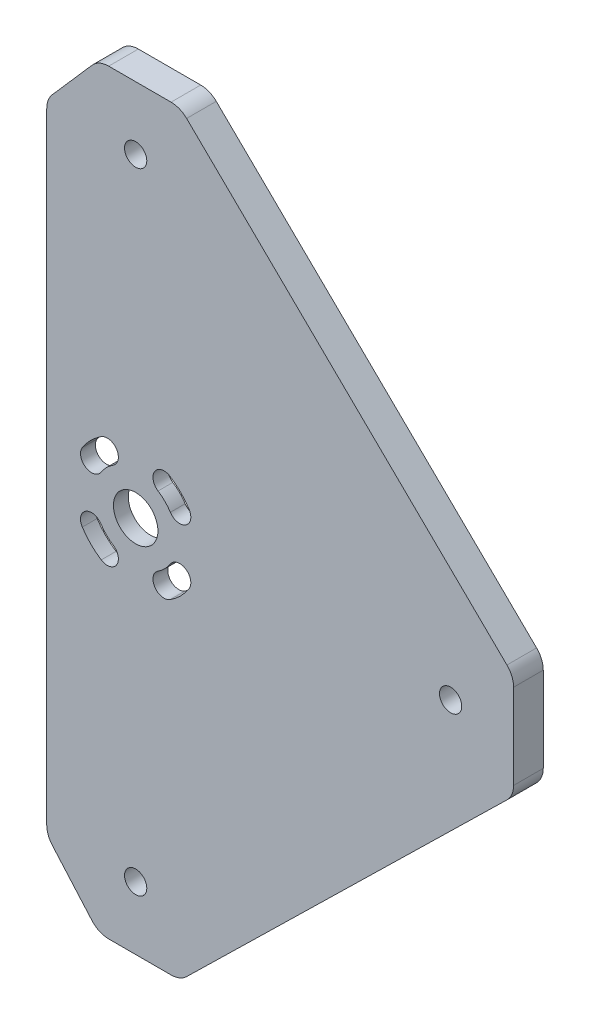
SolidWorks part; units mm, degrees
ref_plane "前视基准面" through (0, 0, 0) normal (0, 0, 1) x (1, 0, 0)
ref_plane "上视基准面" through (0, 0, 0) normal (0, 1, 0) x (1, 0, 0)
ref_plane "右视基准面" through (0, 0, 0) normal (1, 0, 0) x (0, 0, -1)
sketch "草图1" plane through (0, 0, 0) normal (0, 0, 1) x (1, 0, 0)
  line L0 (1791.9751, 1614.3835) -> (1791.9751, 1566.6287) construction
  line L1 (1789.8715, 1561.5082) -> (1789.8715, 1513.7534) construction
  line L2 (1807.2571, 1618.4717) -> (1860.0947, 1562.7534) construction
  line L3 (1860.0947, 1562.7534) -> (1809.6082, 1499.3687) construction
  line L4 (1789.5396, 1516.1637) -> (1794.9009, 1510.0365)
  line L5 (1797.1587, 1509.012) -> (1805.5744, 1509.012)
  line L6 (1807.6718, 1509.867) -> (1850.8947, 1552.1294)
  line L7 (1851.7974, 1554.2744) -> (1851.7974, 1565.7496)
  line L8 (1850.8947, 1567.8946) -> (1807.6718, 1610.157)
  line L9 (1805.5744, 1611.012) -> (1797.1587, 1611.012)
  line L10 (1794.9009, 1609.9875) -> (1789.5396, 1603.8603)
  line L11 (1788.7974, 1601.8848) -> (1788.7974, 1518.1392)
  circle A0 centre (1800.7974, 1560.012) radius 3
  circle A1 centre (1800.7974, 1612.012) radius 1.5 construction
  circle A2 centre (1852.7974, 1560.012) radius 1.5 construction
  circle A3 centre (1800.7974, 1508.012) radius 1.5 construction
  arc A4 (1789.8715, 1513.7534) -> (1809.6082, 1499.3687) centre (1800.7974, 1508.012) ccw construction
  arc A5 (1807.2571, 1618.4717) -> (1791.9751, 1614.3835) centre (1800.7974, 1612.012) ccw construction
  arc A7 (1791.9751, 1566.6287) -> (1789.8715, 1561.5082) centre (1800.7974, 1560.012) ccw construction
  arc A8 (1805.4433, 1552.8093) -> (1808.0001, 1555.3661) centre (1800.7974, 1560.012) ccw
  arc A9 (1808.0001, 1564.6579) -> (1805.4433, 1567.2147) centre (1800.7974, 1560.012) ccw
  arc A10 (1796.1515, 1567.2147) -> (1793.5947, 1564.6579) centre (1800.7974, 1560.012) ccw
  arc A11 (1793.5947, 1555.3661) -> (1796.1515, 1552.8093) centre (1800.7974, 1560.012) ccw
  arc A12 (1803.8171, 1555.3304) -> (1805.479, 1556.9923) centre (1800.7974, 1560.012) ccw
  arc A13 (1805.479, 1563.0318) -> (1803.8171, 1564.6937) centre (1800.7974, 1560.012) ccw
  arc A14 (1797.7776, 1564.6937) -> (1796.1157, 1563.0318) centre (1800.7974, 1560.012) ccw
  arc A15 (1796.1157, 1556.9923) -> (1797.7776, 1555.3304) centre (1800.7974, 1560.012) ccw
  arc A16 (1805.4433, 1567.2147) -> (1803.8171, 1564.6937) centre (1804.6302, 1565.9542) ccw
  arc A17 (1805.479, 1563.0318) -> (1808.0001, 1564.6579) centre (1806.7395, 1563.8448) ccw
  arc A18 (1797.7776, 1564.6937) -> (1796.1515, 1567.2147) centre (1796.9645, 1565.9542) ccw
  arc A19 (1793.5947, 1564.6579) -> (1796.1157, 1563.0318) centre (1794.8552, 1563.8448) ccw
  arc A20 (1796.1157, 1556.9923) -> (1793.5947, 1555.3661) centre (1794.8552, 1556.1792) ccw
  arc A21 (1796.1515, 1552.8093) -> (1797.7776, 1555.3304) centre (1796.9645, 1554.0698) ccw
  arc A22 (1803.8171, 1555.3304) -> (1805.4433, 1552.8093) centre (1804.6302, 1554.0698) ccw
  arc A23 (1808.0001, 1555.3661) -> (1805.479, 1556.9923) centre (1806.7395, 1556.1792) ccw
  circle A24 centre (1800.7974, 1602.512) radius 1.5
  circle A25 centre (1843.2974, 1560.012) radius 1.5
  circle A26 centre (1800.7974, 1517.512) radius 1.5
  arc A27 (1788.7974, 1518.1392) -> (1789.5396, 1516.1637) centre (1791.7974, 1518.1392) ccw
  arc A28 (1794.9009, 1510.0365) -> (1797.1587, 1509.012) centre (1797.1587, 1512.012) ccw
  arc A29 (1805.5744, 1509.012) -> (1807.6718, 1509.867) centre (1805.5744, 1512.012) ccw
  arc A30 (1850.8947, 1552.1294) -> (1851.7974, 1554.2744) centre (1848.7974, 1554.2744) ccw
  arc A31 (1851.7974, 1565.7496) -> (1850.8947, 1567.8946) centre (1848.7974, 1565.7496) ccw
  arc A32 (1807.6718, 1610.157) -> (1805.5744, 1611.012) centre (1805.5744, 1608.012) ccw
  arc A33 (1797.1587, 1611.012) -> (1794.9009, 1609.9875) centre (1797.1587, 1608.012) ccw
  arc A34 (1789.5396, 1603.8603) -> (1788.7974, 1601.8848) centre (1791.7974, 1601.8848) ccw
  dimension "D8" = 52
  dimension "D1" = 52
  dimension "D3" = 4
  dimension "D2" = 52
extrude "凸台-拉伸1" add sketch "草图1" along normal blind 4
sketch "草图3" plane through (0, 0, 0) normal (0, 0, -1) x (-1, 0, 0)
  circle A0 centre (-1800.7974, 1560.012) radius 13
extrude "切除-拉伸2" cut sketch "草图3" against normal blind 2
fillet "圆角1" [suppressed] radius 10
